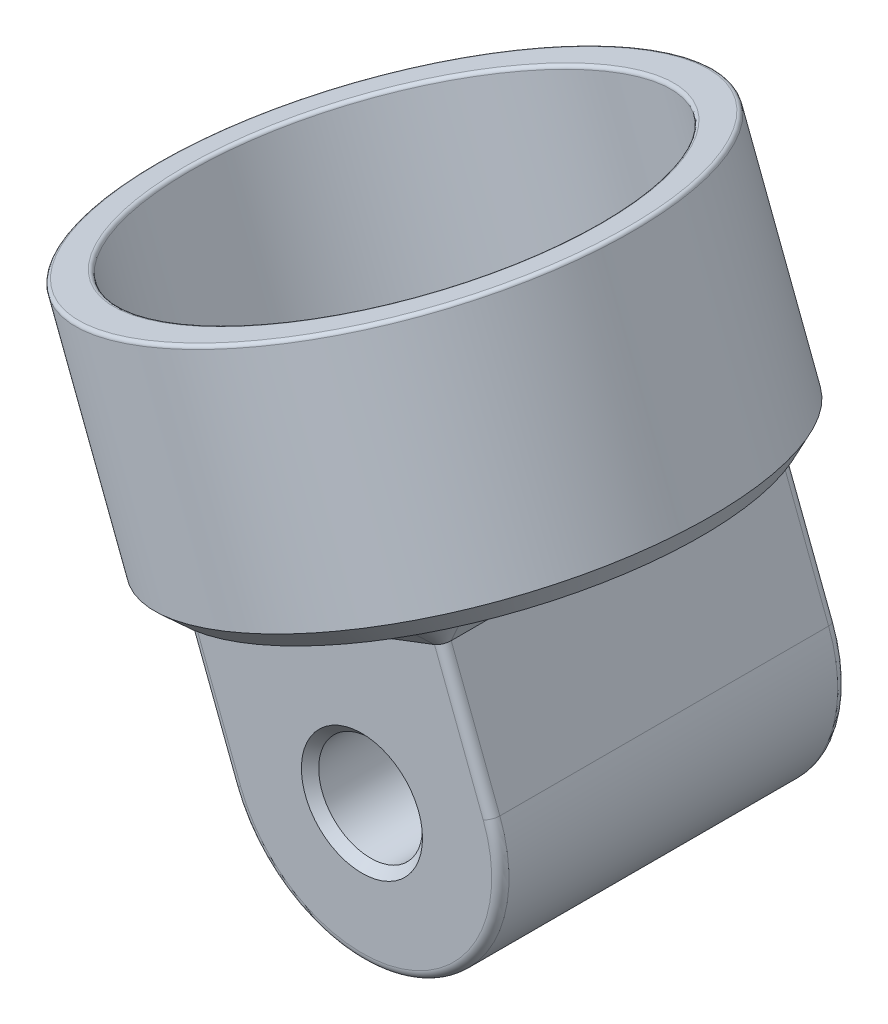
SolidWorks part; units mm, degrees
ref_plane "Front Plane" through (0, 0, 0) normal (0, 0, 1) x (1, 0, 0)
ref_plane "Top Plane" through (0, 0, 0) normal (0, 1, 0) x (1, 0, 0)
ref_plane "Right Plane" through (0, 0, 0) normal (1, 0, 0) x (0, 0, -1)
sketch "Sketch1" plane through (0, 0, 0) normal (0, 0, 1) x (1, 0, 0)
  line L1 (2.9256, 48.9181) -> (97.0713, 14.6519)
  line L2 (97.0713, 14.6519) -> (114.1723, 61.6365) construction
  line L3 (2.9256, 48.9181) -> (16.6344, 86.5828) construction
  line L4 (64.2, 56.8) -> (64.2, 145) construction
  line L5 (17.2835, 64.9758) -> (54.2, 106.8)
  line L6 (74.2, 121.8) -> (101.5245, 50.2773)
  line L7 (40.7, 148) -> (40.7, 52.5253) construction
  line L8 (87.7, 148) -> (87.7, 56.8) construction
  arc A1 (97.0713, 14.6519) -> (108.8436, 11.9213) centre (114.1723, 61.6365) ccw
  circle A2 centre (17.2835, 64.9758) radius 3
  circle A3 centre (101.5245, 50.2773) radius 3
  circle A8 centre (74.2, 121.8) radius 3
  circle A9 centre (54.2, 106.8) radius 3
  spline S1 degree 3 poles (108.8436, 11.9213) (110.0019, 11.7972) (111.159, 11.6604) (114.5227, 11.2279) (116.7249, 10.9021) (123.3121, 9.8294) (127.6782, 8.9871) (140.7169, 6.3137) (149.3307, 4.3374) (166.474, 1.206) (175.0008, 0.0515) (187.7816, -0.2014) (192.0406, -0.0398) (200.5758, 0.9156) (204.8521, 1.7093) (209.1515, 2.8921) knots 0.514918 0.514918 0.514918 0.514918 0.53125 0.53125 0.5625 0.5625 0.625 0.625 0.75 0.75 0.875 0.875 0.9375 0.9375 1 1 1 1
  point P0 (64.2, 56.8)
  point P18 (17.2835, 64.9758)
  point P19 (101.5245, 50.2773)
  point P26 (74.2, 121.8)
  point P27 (54.2, 106.8)
  point P31 (87.8622, 86.0387)
  point P32 (35.7418, 85.8879)
  dimension "D11" = 6
  dimension "D12" = 6
  dimension "D15" = 46.9165
  dimension "D17" = 6
  dimension "D18" = 6
  dimension "D3" = 20
  dimension "D4" = 35
  dimension "D5" = 8
  dimension "D6" = 10
  dimension "D7" = 8
  dimension "D8" = 10
  dimension "D9" = 65
  dimension "D10" = 50
  dimension "D13" = 37.3245
  dimension "D14" = 6.5227
  dimension "D16" = 8.1758
sketch "Sketch2" plane through (0, 0, 0) normal (0, 0, 1) x (1, 0, 0)
  line L0 (94.0513, 47.4223) -> (89.9892, 58.055)
  line L2 (89.9892, 58.055) -> (104.9355, 63.7651)
  line L3 (108.9977, 53.1324) -> (104.9355, 63.7651)
  line L6 (74.2, 121.8) -> (101.5245, 50.2773) construction
  circle A1 centre (101.5245, 50.2773) radius 3
  arc A2 (94.0513, 47.4223) -> (108.9977, 53.1324) centre (101.5245, 50.2773) ccw
  point P4 (98.9582, 56.9946)
  dimension "D1" = 5
  dimension "D2" = 11.3822
extrude "Boss-Extrude1" add sketch "Sketch2" along normal blind 10 and the other way blind 10 separate body
sketch "Sketch3" plane through (-7.893, 20.6602, 0) normal (-0.3569, 0.9341, 0) x (0.9341, 0.3569, 0)
  circle A1 centre (112.7821, 0) radius 15.7
  dimension "D1" = 31.4
extrude "Boss-Extrude2" add sketch "Sketch3" along normal blind 1.5 and the other way blind 2.5
sketch "Sketch4" plane through (-8.4283, 22.0614, 0) normal (-0.3569, 0.9341, 0) x (0.9341, 0.3569, 0)
  circle A0 centre (112.7821, 0) radius 15.7
  circle A1 centre (112.7821, 0) radius 12.7
  dimension "D1" = 25.4
  dimension "D2" = 3
extrude "Boss-Extrude4" add sketch "Sketch4" along normal blind 10
fillet "Fillet6" radius 0.5 6 edges at (107.4127, 57.281, -10) (104.3795, 42.8041, -10) (92.4663, 51.5709, -10) (107.4127, 57.281, 10) (104.3795, 42.8041, 10) (92.4663, 51.5709, 10)
chamfer "Chamfer1" distance 0.5 angle 45 2 edges at (104.5245, 50.2773, 10) (104.5245, 50.2773, -10)
sketch "Sketch5" plane through (-11.9971, 31.4029, 0) normal (-0.3569, 0.9341, 0) x (0.9341, 0.3569, 0)
  circle A0 centre (112.7821, 0) radius 12.7
  circle A1 centre (112.7821, 0) radius 14.7
  circle A2 centre (112.7821, 0) radius 19.899
  circle M1 centre (112.7821, 0) radius 15.7
  dimension "D1" = 25.4
  dimension "D2" = 2
extrude "Cut-Extrude2" cut sketch "Sketch5" against normal through all contours A2 M1 | A1 M1 region at (75.2953, 64.752, 0) region at (79.1069, 66.2082, 0)
fillet "Fillet7" radius 0.2 2 edges at (79.6262, 66.4066, 0) (81.4945, 67.1204, 0)
chamfer "Chamfer3" distance 1 angle 45 9 edges at (84.6226, 53.3285, 0) (105.6909, 61.3774, 9.8536) (98.3546, 58.5747, 10) (91.0182, 55.7719, 9.8536) (90.8814, 55.7196, 0) (91.0182, 55.7719, -9.8536) (98.3546, 58.5747, -10) (105.6909, 61.3774, -9.8536) (105.8278, 61.4297, 0)
